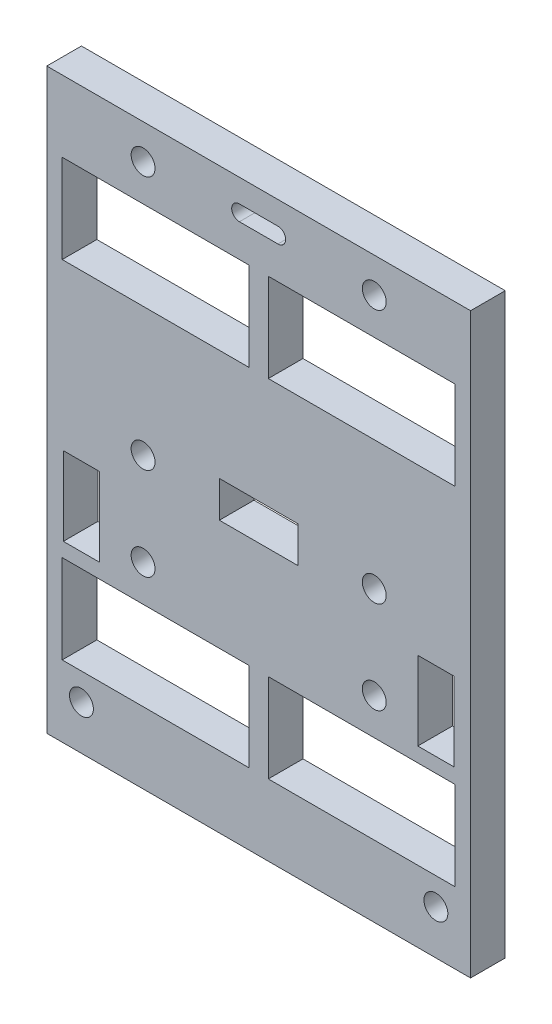
SolidWorks part; units mm, degrees
ref_plane "Front Plane" through (0, 0, 0) normal (0, 0, 1) x (1, 0, 0)
ref_plane "Top Plane" through (0, 0, 0) normal (0, 1, 0) x (1, 0, 0)
ref_plane "Right Plane" through (0, 0, 0) normal (1, 0, 0) x (0, 0, -1)
sketch "Sketch1" plane through (0, 0, 0) normal (0, 0, 1) x (1, 0, 0)
  line L0 (0, -37.5) -> (0, 37.5) construction
  line L1 (-27.5, -37.5) -> (27.5, -37.5)
  line L2 (-27.5, -37.5) -> (-27.5, 37.5)
  line L3 (-27.5, 37.5) -> (27.5, 37.5)
  line L4 (27.5, -37.5) -> (27.5, 37.5)
  line L5 (-27.5, -37.5) -> (27.5, 37.5) construction
  line L6 (-27.5, 37.5) -> (27.5, -37.5) construction
  line L7 (-27.5, 0) -> (27.5, 0) construction
  line L8 (-27.5, 22.5) -> (27.5, 22.5) construction
  line L9 (25.5, 16.75) -> (1.25, 28.25) construction
  line L10 (-25.5, 28.25) -> (-1.25, 28.25)
  line L11 (-25.5, 28.25) -> (-25.5, 16.75)
  line L12 (-25.5, 16.75) -> (-1.25, 16.75)
  line L13 (-1.25, 28.25) -> (-1.25, 16.75)
  line L14 (-25.5, 28.25) -> (-1.25, 16.75) construction
  line L15 (-25.5, 16.75) -> (-1.25, 28.25) construction
  line L16 (25.5, 28.25) -> (1.25, 16.75) construction
  line L17 (1.25, 28.25) -> (1.25, 16.75)
  line L18 (25.5, 16.75) -> (1.25, 16.75)
  line L19 (25.5, 28.25) -> (25.5, 16.75)
  line L20 (25.5, 28.25) -> (1.25, 28.25)
  line L21 (25.5, -28.25) -> (1.25, -16.75) construction
  line L22 (-25.5, -16.75) -> (-1.25, -28.25) construction
  line L23 (-25.5, -28.25) -> (-1.25, -16.75) construction
  line L24 (25.5, -16.75) -> (1.25, -28.25) construction
  line L25 (25.5, -28.25) -> (1.25, -28.25)
  line L26 (25.5, -28.25) -> (25.5, -16.75)
  line L27 (25.5, -16.75) -> (1.25, -16.75)
  line L28 (1.25, -28.25) -> (1.25, -16.75)
  line L29 (-1.25, -28.25) -> (-1.25, -16.75)
  line L30 (-25.5, -16.75) -> (-1.25, -16.75)
  line L31 (-25.5, -28.25) -> (-25.5, -16.75)
  line L32 (-25.5, -28.25) -> (-1.25, -28.25)
  point P0 (0, 0)
  point P12 (-13.375, 22.5)
  point P21 (13.375, 22.5)
  point P30 (13.375, -22.5)
  point P31 (-13.375, -22.5)
  dimension "D1" = 55
  dimension "D2" = 75
  dimension "D3" = 22.5
  dimension "D4" = 24.25
  dimension "D5" = 11.5
  dimension "D6" = 1.25
extrude "Boss-Extrude1" add sketch "Sketch1" along normal blind 4.5
sketch "Sketch2" plane through (0, 0, 4.5) normal (0, 0, 1) x (1, 0, 0)
  line L0 (0, -37.5) -> (0, 37.5) construction
  line L1 (-27.5, -37.5) -> (27.5, -37.5) construction
  line L2 (27.5, 37.5) -> (-27.5, 37.5) construction
  line L3 (-27.5, 0) -> (27.5, 0) construction
  line L4 (-27.5, 37.5) -> (-27.5, -37.5) construction
  line L5 (27.5, -37.5) -> (27.5, 37.5) construction
  line L6 (-15, 0) -> (15, 0) construction
  circle A0 centre (-15, 33) radius 1.55
  circle A1 centre (15, 33) radius 1.55
  circle A2 centre (15, 0) radius 1.55
  circle A3 centre (-15, 0) radius 1.55
  dimension "D1" = 3.1
  dimension "D7" = 3.1
  dimension "D8" = 3.1
  dimension "D2" = 15
  dimension "D3" = 33
  dimension "D4" = 30
  dimension "D5" = 15
  dimension "D6" = 0
extrude "screwHoles" cut sketch "Sketch2" against normal through all
sketch "Sketch3" plane through (0, 0, 4.5) normal (0, 0, 1) x (1, 0, 0)
  line L0 (-27.5, 9) -> (26.0486, 9) construction
  line L1 (-27.5, 37.5) -> (-27.5, -37.5) construction
  line L3 (0, 37.5) -> (0, -37.5) construction
  line L4 (27.5, 37.5) -> (-27.5, 37.5) construction
  line L5 (-27.5, -37.5) -> (27.5, -37.5) construction
  line L6 (19.1, 6.65) -> (8.9, 11.35) construction
  line L7 (-19.1, 11.35) -> (-8.9, 11.35)
  line L8 (-19.1, 11.35) -> (-19.1, 6.65)
  line L9 (-19.1, 6.65) -> (-8.9, 6.65)
  line L10 (-8.9, 11.35) -> (-8.9, 6.65)
  line L11 (-19.1, 11.35) -> (-8.9, 6.65) construction
  line L12 (-19.1, 6.65) -> (-8.9, 11.35) construction
  line L13 (19.1, 11.35) -> (8.9, 6.65) construction
  line L14 (8.9, 11.35) -> (8.9, 6.65)
  line L15 (19.1, 6.65) -> (8.9, 6.65)
  line L16 (19.1, 11.35) -> (19.1, 6.65)
  line L17 (19.1, 11.35) -> (8.9, 11.35)
  line L18 (-27.5, 37.5) -> (-27.5, -37.5) construction
  point P2 (-27.5, 0)
  point P12 (-14, 9)
  point P21 (14, 9)
  dimension "D1" = 10.2
  dimension "D2" = 4.7
  dimension "D3" = 14
  dimension "D4" = 9
extrude "BeltClamp" [suppressed] cut sketch "Sketch3" against normal through all
sketch "Sketch4" plane through (0, 0, 4.5) normal (0, 0, 1) x (1, 0, 0)
  line L0 (-27.5, 0) -> (27.5, 0) construction
  line L1 (-27.5, 37.5) -> (-27.5, -37.5) construction
  line L2 (27.5, -37.5) -> (27.5, 37.5) construction
  line L4 (-5.1, 2.35) -> (5.1, 2.35)
  line L5 (-5.1, 2.35) -> (-5.1, -2.35)
  line L6 (-5.1, -2.35) -> (5.1, -2.35)
  line L7 (5.1, 2.35) -> (5.1, -2.35)
  line L8 (-5.1, 2.35) -> (5.1, -2.35) construction
  line L9 (-5.1, -2.35) -> (5.1, 2.35) construction
  circle A0 centre (-15, 0) radius 1.55 construction
  point P6 (0, 0)
  dimension "D1" = 10.2
  dimension "D2" = 4.7
  dimension "D3" = 0
extrude "mountingPlateTab" cut sketch "Sketch4" against normal through all
sketch "Sketch5" plane through (0, 0, 4.5) normal (0, 0, 1) x (1, 0, 0)
  line L0 (-27.5, -9.75) -> (27.5, -9.75) construction
  line L1 (-27.5, 37.5) -> (-27.5, -37.5) construction
  line L2 (27.5, -37.5) -> (27.5, 37.5) construction
  line L4 (0, -37.5) -> (0, 37.5) construction
  line L5 (-27.5, -37.5) -> (27.5, -37.5) construction
  line L6 (27.5, 37.5) -> (-27.5, 37.5) construction
  line L7 (-20.65, -14.85) -> (-25.35, -4.65) construction
  line L8 (20.65, -4.65) -> (25.35, -4.65)
  line L9 (20.65, -4.65) -> (20.65, -14.85)
  line L10 (20.65, -14.85) -> (25.35, -14.85)
  line L11 (25.35, -4.65) -> (25.35, -14.85)
  line L12 (20.65, -4.65) -> (25.35, -14.85) construction
  line L13 (20.65, -14.85) -> (25.35, -4.65) construction
  line L14 (-20.65, -4.65) -> (-25.35, -14.85) construction
  line L15 (-25.35, -4.65) -> (-25.35, -14.85)
  line L16 (-20.65, -14.85) -> (-25.35, -14.85)
  line L17 (-20.65, -4.65) -> (-20.65, -14.85)
  line L18 (-20.65, -4.65) -> (-25.35, -4.65)
  line L19 (23, -9.75) -> (23, -37.5) construction
  line L20 (-23, -9.75) -> (-23, -37.5) construction
  circle A0 centre (23, -31.75) radius 1.55
  circle A1 centre (-23, -31.75) radius 1.55
  point P15 (23, -9.75)
  point P24 (-23, -9.75)
  dimension "D5" = 3.1
  dimension "D2" = 10.2
  dimension "D3" = 4.7
  dimension "D4" = 23
  dimension "D6" = 22
  dimension "D1" = 9.75
extrude "BraceTabs" cut sketch "Sketch5" against normal through all
sketch "Sketch6" plane through (0, 0, 4.5) normal (0, 0, 1) x (1, 0, 0)
  line L0 (-25.35, -9.75) -> (25.35, -9.75) construction
  line L1 (-25.35, -4.65) -> (-25.35, -14.85) construction
  line L2 (25.35, -14.85) -> (25.35, -4.65) construction
  line L3 (0, -2.35) -> (0, -37.5) construction
  line L4 (-5.1, -2.35) -> (5.1, -2.35) construction
  line L5 (-27.5, -37.5) -> (27.5, -37.5) construction
  line L6 (23, -14.85) -> (23, -4.65) construction
  line L7 (20.65, -14.85) -> (25.35, -14.85) construction
  line L8 (25.35, -4.65) -> (20.65, -4.65) construction
  line L9 (20.65, -4.65) -> (20.65, -14.85) construction
  line L10 (19.65, -15.85) -> (26.35, -15.85)
  line L11 (19.65, -15.85) -> (19.65, -3.65)
  line L12 (19.65, -3.65) -> (26.35, -3.65)
  line L13 (26.35, -15.85) -> (26.35, -3.65)
  line L14 (19.65, -15.85) -> (26.35, -3.65) construction
  line L15 (19.65, -3.65) -> (26.35, -15.85) construction
  line L16 (-19.65, -3.65) -> (-26.35, -15.85) construction
  line L17 (-19.65, -15.85) -> (-26.35, -3.65) construction
  line L18 (-23, -14.85) -> (-23, -4.65) construction
  line L19 (-26.35, -15.85) -> (-26.35, -3.65)
  line L20 (-19.65, -3.65) -> (-26.35, -3.65)
  line L21 (-19.65, -15.85) -> (-19.65, -3.65)
  line L22 (-19.65, -15.85) -> (-26.35, -15.85)
  circle A0 centre (23, -9.75) radius 1.55
  circle A1 centre (-23, -9.75) radius 1.55
  point P18 (23, -9.75)
  dimension "D3" = 3.1
  dimension "D1" = 1
  dimension "D2" = 1
extrude "FrontToRear1" [suppressed] add sketch "Sketch6" against normal up to surface (4.5 mm away) up to face at (-24.55, -31.75, 0)
sketch "Sketch7" plane through (0, 0, 4.5) normal (0, 0, 1) x (1, 0, 0)
  line L0 (5.1, 2.35) -> (-5.1, 2.35) construction
  line L1 (-20, -3.35) -> (20, -3.35)
  line L2 (-20, -3.35) -> (-20, 3.35)
  line L3 (-20, 3.35) -> (20, 3.35)
  line L4 (20, -3.35) -> (20, 3.35)
  line L5 (-20, -3.35) -> (20, 3.35) construction
  line L6 (-20, 3.35) -> (20, -3.35) construction
  circle A0 centre (15, 0) radius 1.55 construction
  point P0 (0, 0)
  dimension "D1" = 1
  dimension "D2" = 5
extrude "FrontToRear2" [suppressed] add sketch "Sketch7" against normal through all
sketch "Sketch8" plane through (0, 0, 4.5) normal (0, 0, 1) x (1, 0, 0)
  line L0 (-27.5, -12) -> (27.5, -12) construction
  line L1 (-27.5, 37.5) -> (-27.5, -37.5) construction
  line L2 (27.5, -37.5) -> (27.5, 37.5) construction
  line L3 (0, -37.5) -> (0, 0) construction
  line L4 (-27.5, -37.5) -> (27.5, -37.5) construction
  circle A0 centre (-15, -12) radius 1.55
  circle A1 centre (15, -12) radius 1.55
  dimension "D2" = 3.1
  dimension "D1" = 12
  dimension "D3" = 15
extrude "ExpansionScrewholes" cut sketch "Sketch8" against normal through all
sketch "Sketch12" plane through (0, 0, 4.5) normal (0, 0, 1) x (1, 0, 0)
  line L0 (0, 37.5) -> (0, 0) construction
  line L1 (27.5, 37.5) -> (-27.5, 37.5) construction
  line L2 (-2.5, 33.5) -> (2.5, 33.5) construction
  line L3 (-2.5, 34.5) -> (2.5, 34.5)
  line L4 (-2.5, 32.5) -> (2.5, 32.5)
  arc A0 (-2.5, 34.5) -> (-2.5, 32.5) centre (-2.5, 33.5) ccw
  arc A1 (2.5, 32.5) -> (2.5, 34.5) centre (2.5, 33.5) ccw
  point P7 (0, 33.5)
  dimension "D1" = 3
  dimension "D2" = 2
  dimension "D3" = 5
extrude "CableTieSlot" cut sketch "Sketch12" against normal through all
sketch "Sketch11" [suppressed] plane through (0, 0, 4.5) normal (0, 0, 1) x (1, 0, 0)
  line L0 (13.5615, -8.85) -> (27.5, -8.85) construction
  line L1 (27.5, -37.5) -> (27.5, 37.5) construction
  line L2 (0, 37.5) -> (0, -37.5) construction
  line L3 (36.5, -14.85) -> (18.5, -14.85)
  line L4 (36.5, -14.85) -> (36.5, -2.85)
  line L5 (36.5, -2.85) -> (18.5, -2.85)
  line L6 (18.5, -14.85) -> (18.5, -2.85)
  line L7 (36.5, -14.85) -> (18.5, -2.85) construction
  line L8 (36.5, -2.85) -> (18.5, -14.85) construction
  line L11 (-36.5, -2.85) -> (-18.5, -14.85) construction
  line L12 (-36.5, -14.85) -> (-18.5, -2.85) construction
  line L13 (-18.5, -14.85) -> (-18.5, -2.85)
  line L14 (-36.5, -2.85) -> (-18.5, -2.85)
  line L15 (-36.5, -14.85) -> (-36.5, -2.85)
  line L16 (-36.5, -14.85) -> (-18.5, -14.85)
  line L17 (36.5, -2.85) -> (18.5, -14.85) construction
  line L18 (20.65, -14.85) -> (25.35, -14.85) construction
  line L19 (27.5, 37.5) -> (-27.5, 37.5) construction
  line L20 (-27.5, -37.5) -> (27.5, -37.5) construction
  dimension "D1" = 9
  dimension "D2" = 12
  dimension "D3" = 0
extrude "Cut-Extrude2" [suppressed] cut sketch "Sketch11" against normal through all
sketch "Sketch10" plane through (0, 0, 4.5) normal (0, 0, 1) x (1, 0, 0)
  line L0 (4.7446, 1) -> (27.5, 1) construction
  line L1 (-5.1, 0) -> (5.1, 0) construction
  line L2 (27.5, -37.5) -> (27.5, 37.5) construction
  line L3 (0, 2.35) -> (0, -2.35) construction
  line L4 (36.5, 4) -> (18.5, 4)
  line L5 (36.5, 4) -> (36.5, -2)
  line L6 (36.5, -2) -> (18.5, -2)
  line L7 (18.5, 4) -> (18.5, -2)
  line L8 (36.5, 4) -> (18.5, -2) construction
  line L9 (36.5, -2) -> (18.5, 4) construction
  line L10 (5.1, 2.35) -> (-5.1, 2.35) construction
  line L11 (-5.1, -2.35) -> (5.1, -2.35) construction
  line L12 (-36.5, -2) -> (-18.5, 4) construction
  line L13 (-36.5, 4) -> (-18.5, -2) construction
  line L14 (-4.7446, 1) -> (-27.5, 1) construction
  line L15 (-18.5, 4) -> (-18.5, -2)
  line L16 (-36.5, -2) -> (-18.5, -2)
  line L17 (-36.5, 4) -> (-36.5, -2)
  line L18 (-36.5, 4) -> (-18.5, 4)
  line L19 (36.5, -2) -> (18.5, 4) construction
  line L20 (-5.1, 2.35) -> (-5.1, -2.35) construction
  line L21 (5.1, -2.35) -> (5.1, 2.35) construction
  dimension "D1" = 6
  dimension "D2" = 9
  dimension "D3" = 1
extrude "CableTieSlots" [suppressed] cut sketch "Sketch10" against normal through all
sketch "Sketch9" [suppressed] plane through (0, 0, 4.5) normal (0, 0, 1) x (1, 0, 0)
  line L0 (-27.5, -37.5) -> (27.5, -37.5) construction
  line L5 (-9, -42.5) -> (9, -42.5)
  line L6 (-9, -42.5) -> (-9, -34.5)
  line L7 (-7, -32.5) -> (7, -32.5)
  line L8 (9, -42.5) -> (9, -34.5)
  line L9 (-9, -42.5) -> (9, -32.5) construction
  line L10 (-9, -32.5) -> (9, -42.5) construction
  arc A0 (7, -32.5) -> (9, -34.5) centre (7, -34.5) cw
  arc A1 (-9, -34.5) -> (-7, -32.5) centre (-7, -34.5) cw
  point P9 (0, -37.5)
  line M42 (-27.5, -37.5) -> (27.5, -37.5)
  dimension "D3" = 2
  dimension "D1" = 18
  dimension "D2" = 5
extrude "RearFanSlot" [suppressed] cut sketch "Sketch9" against normal through all contours A1 L6 L8 A0 L7 M42 | L5 L8 L6 M42
sketch "Sketch13" [suppressed] plane through (0, 0, 4.5) normal (0, 0, 1) x (1, 0, 0)
  line L1 (-7, -2.85) -> (7, -2.85)
  line L2 (-7, -2.85) -> (-7, -11.85)
  line L3 (-7, -11.85) -> (7, -11.85)
  line L4 (7, -2.85) -> (7, -11.85)
  line L5 (-7, -2.85) -> (7, -11.85) construction
  line L6 (-7, -11.85) -> (7, -2.85) construction
  line L9 (0, 37.5) -> (0, -7.35) construction
  line L10 (-18.5, -2.85) -> (-27.5, -2.85) construction
  line L11 (27.5, 37.5) -> (-27.5, 37.5) construction
  line L13 (-27.5, -14.85) -> (-18.5, -14.85) construction
  point P0 (0, -7.35)
  dimension "D1" = 3
  dimension "D2" = 0
  dimension "D3" = 7
extrude "Cut-Extrude3" [suppressed] cut sketch "Sketch13" against normal through all
equation "\"X-ROD-SPACING\"=45"
equation "\"Y-ROD-SPACING\"=75"
equation "\"Z-ROD-SPACING\"=17.5"
equation "\"Y-BED-OFFSET\"=2"
equation "\"Y-BED-ROD-INSET\"=3.5"
equation "\"Y-BED-SCREW-SPACING\"=209"
equation "\"Y-BED-SCREW-CUTOUT-SLOT-HEIGHT\"=2"
equation "\"T-SLOT-NUT-FILLET-RADIUS\"=0.25"
equation "\"T-SLOT-SCREW-SHAFT-RADIUS\"=1.75"
equation "\"T-SLOT-SCREW-SHAFT-CUTOUT-LENGTH\"=10.5"
equation "\"T-SLOT-NUT-DEPTH\"=4.2"
equation "\"T-SLOT-NUT-WIDTH\"=3"
equation "\"T-SLOT-NUT-END-DISTANCE\"=8"
equation "\"ACRYLIC-THICKNESS\"=10"
equation "\"ACRYLIC-THICKNESS2\"=4.5"
equation "\"ACRYLIC-TAB-CUTOUT-SIZE\"=\"ACRYLIC-THICKNESS\"+\"ACRYLIC-TAB-TOLERANCE\"*2"
equation "\"ACRYLIC-TAB-WIDTH\"=\"ACRYLIC-THICKNESS\""
equation "\"ACRYLIC-M3-HOLE\"=3.1"
equation "\"SMOOTHROD-CAP-SCREW-DISTANCE\"=20"
equation "\"FRAME-WIDTH-INNER\"=370"
equation "\"NEMA17-HOLE-SPACING\"=31"
equation "\"NEMA17-CENTRAL-CUTOUT\"=22.5"
equation "\"Z-BRACKET-REACH\"=55"
equation "\"Z-ROD-INSET\"=16"
equation "\"TOP-BRACKET-SPACING\"=40"
equation "\"SMOOTHROD-X-LENGTH\"=350"
equation "\"SMOOTHROD-Y-LENGTH\"=350"
equation "\"SMOOTHROD-Z-LENGTH\"=350"
equation "\"SMOOTHROD-TIGHTENING-HEADROOM\"=.25"
equation "\"LEADSCREW-Z-LENGTH\"=300"
equation "\"SCREW-LENGTH-FRAME\"=\"ACRYLIC-THICKNESS\" + 10"
equation "\"SCREW-LENGTH-MOTOR\"=\"ACRYLIC-THICKNESS\" + 5"
equation "\"SCREW-HEAD-RADIUS\"=6"
equation "\"PRINTED-X-SMOOTHROD-DIAMETER\"=8.2"
equation "\"PRINTED-X-SMOOTHROD-CUTOUT\"=10"
equation "\"PRINTED-X-BASE-HEIGHT\"=10"
equation "\"PRINTED-LM8UU-CUTOUT-SIZE\"=15.25"
equation "\"PRINTED-LM8UU-CUTOUT-LENGTH\"=24.5"
equation "\"PRINTED-X-IDLER-HEIGHT\"=16"
equation "\"PSU-MOUNTING-WIDTH\"=95"
equation "\"PSU-MOUNTING-HEIGHT\"=177"
equation "\"Y-BELT-TO-ROD-DISTANCE\"=20"
equation "\"SPOOL-HOLDER-ROD-SPACING\"=150"
equation "\"D3@Sketch1\"=\"X-ROD-SPACING\"/2"
equation "\"D4@Sketch1\"=\"ACRYLIC-X-CARRIAGE-LM8UU-CUTOUT-WIDTH\""
equation "\"D1@Boss-Extrude1\"=\"ACRYLIC-THICKNESS2\""
equation "\"D1@Sketch2\"=\"ACRYLIC-M3-HOLE\""
equation "\"D1@Sketch3\"=\"ACRYLIC-TAB-CUTOUT-SIZE\""
equation "\"D2@Sketch3\"=\"ACRYLIC-THICKNESS2\"+\"ACRYLIC-TAB-TOLERANCE\"*2"
equation "\"ACRYLIC-X-CARRIAGE-WIDTH\"=55"
equation "\"ACRYLIC-X-CARRIAGE-HEIGHT\"=75"
equation "\"D1@Sketch1\"=\"ACRYLIC-X-CARRIAGE-WIDTH\""
equation "\"D2@Sketch1\"=\"ACRYLIC-X-CARRIAGE-HEIGHT\""
equation "\"ACRYLIC-X-CARRIAGE-CENTER-TAB-SPACING\"=14"
equation "\"D3@Sketch3\"=\"ACRYLIC-X-CARRIAGE-CENTER-TAB-SPACING\""
equation "\"SCREW-LENGTH-EXTRUDER\"=28"
equation "\"ACRYLIC-X-CARRIAGE-SCREW-SPACING-X\"=15"
equation "\"ACRYLIC-X-CARRIAGE-SCREW-SPACING-Y\"=33"
equation "\"D2@Sketch2\"=\"ACRYLIC-X-CARRIAGE-SCREW-SPACING-X\""
equation "\"D3@Sketch2\"=\"ACRYLIC-X-CARRIAGE-SCREW-SPACING-Y\""
equation "\"D1@Sketch4\"=\"ACRYLIC-TAB-CUTOUT-SIZE\""
equation "\"D2@Sketch4\"=\"ACRYLIC-THICKNESS2\"+\"ACRYLIC-TAB-TOLERANCE\"*2"
equation "\"D2@Sketch5\"=\"ACRYLIC-TAB-CUTOUT-SIZE\""
equation "\"D3@Sketch5\"=\"ACRYLIC-THICKNESS2\"+\"ACRYLIC-TAB-TOLERANCE\"*2"
equation "\"ACRYLIC-X-CARRIAGE-EXTRUDER-SHELF-DEPTH\"=\"ACRYLIC-X-CARRIAGE-EXTRUDER-OFFSET\" + 28"
equation "\"ACRYLIC-X-CARRIAGE-EXTRUDER-BRACE-SPACING\"=23"
equation "\"D4@Sketch5\"=\"ACRYLIC-X-CARRIAGE-EXTRUDER-BRACE-SPACING\""
equation "\"D4@Sketch2\"=\"ACRYLIC-X-CARRIAGE-SCREW-SPACING-X\"*2"
equation "\"D5@Sketch2\"=\"ACRYLIC-X-CARRIAGE-SCREW-SPACING-X\""
equation "\"D7@Sketch2\"=\"ACRYLIC-M3-HOLE\""
equation "\"D8@Sketch2\"=\"ACRYLIC-M3-HOLE\""
equation "\"ACRYLIC-X-CARRIAGE-LM8UU-CUTOUT-WIDTH\"=24.25"
equation "\"ACRYLIC-TAB-TOLERANCE\"=.1"
equation "\"ACRYLIC-X-CARRIAGE-EXTRUDER-OFFSET\"=26"
equation "\"ACRYLIC-X-CARRIAGE-EXTRUDER-ANGLE\"=90"
equation "\"ACRYLIC-X-CARRIAGE-EXTRUDER-BRACE-TAB-OFFSET\"=20"
equation "\"ACRYLIC-X-CARRIAGE-EXTRUDER-BRACE-HEIGHT\"=35"
equation "\"ACRYLIC-X-CARRIAGE-EXTRUDER-BRACE-SCREW-SPACING\"=22"
equation "\"D5@Sketch5\"=\"ACRYLIC-M3-HOLE\""
equation "\"D3@Sketch6\"=\"ACRYLIC-M3-HOLE\""
equation "\"ACRYLIC-X-CARRIAGE-LM8UU-CUTOUT-HEIGHT\"=11.5"
equation "\"ACRYLIC-X-CARRIAGE-DUAL-WIDTH-MULTIPLIER\"=1.65"
equation "\"ACRYLIC-X-CARRIAGE-DUAL-HOTEND-SPACING\"=42"
equation "\"ACRYLIC-X-CARRIAGE-DUAL-WIDTH\"=75"
equation "\"ACRYLIC-X-CARRIAGE-DUAL-HOTEND-SEPARATION\"=36"
equation "\"ACRYLIC-X-CARRIAGE-DUAL-MOUNT-PLATE-DEPTH\"=75"
equation "\"ACRYLIC-X-CARRIAGE-DUAL-MOUNT-BRACE-WIDTH\"=33"
equation "\"ACRYLIC-X-CARRIAGE-DUAL-MOUNT-SCREW-WIDTH\"=40"
equation "\"D5@Sketch1\"=\"ACRYLIC-X-CARRIAGE-LM8UU-CUTOUT-HEIGHT\""
equation "\"D2@Sketch8\"=\"ACRYLIC-M3-HOLE\""
equation "\"D1@Sketch5\"=\"ACRYLIC-THICKNESS2\"/2 + 7.5"
